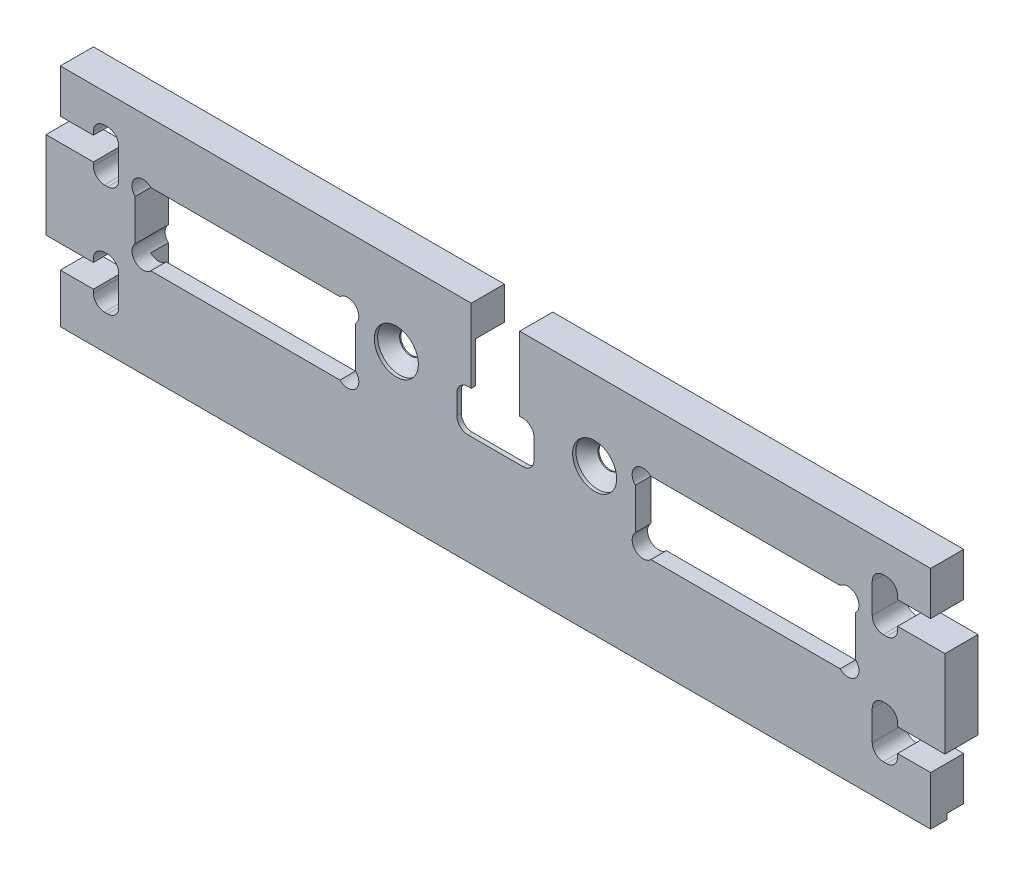
SolidWorks part; units mm, degrees
ref_plane "Front Plane" through (0, 0, 0) normal (0, 0, 1) x (1, 0, 0)
ref_plane "Top Plane" through (0, 0, 0) normal (0, 1, 0) x (1, 0, 0)
ref_plane "Right Plane" through (0, 0, 0) normal (1, 0, 0) x (0, 0, -1)
sketch "Sketch1" plane through (0, 0, 0) normal (0, 0, 1) x (1, 0, 0)
  line L0 (-39.5, 0) -> (39.5, 0) construction
  line L1 (-39.5, 10) -> (39.5, 10)
  line L2 (-39.5, 10) -> (-39.5, -10)
  line L3 (-39.5, -10) -> (39.5, -10)
  line L4 (39.5, 10) -> (39.5, -10)
  line L5 (-39.5, 10) -> (39.5, -10) construction
  line L6 (-39.5, -10) -> (39.5, 10) construction
  line L7 (0, 10) -> (0, -10) construction
  line L9 (-40.8, -3.95) -> (-39.5, -3.95)
  line L10 (-40.8, -3.95) -> (-40.8, 3.95)
  line L11 (-40.8, 3.95) -> (-39.5, 3.95)
  line L12 (-39.5, -3.95) -> (-39.5, 3.95)
  line L13 (-40.8, -3.95) -> (-39.5, 3.95) construction
  line L14 (-40.8, 3.95) -> (-39.5, -3.95) construction
  line L16 (40.8, 3.95) -> (39.5, 3.95)
  line L17 (40.8, -3.95) -> (40.8, 3.95)
  line L18 (40.8, -3.95) -> (39.5, -3.95)
  line L19 (-39.5, 5) -> (39.5, 5) construction
  line L20 (-35.35, 7.35) -> (-35.35, 2.65) construction
  line L21 (-36.5, 3.95) -> (-39.5, 3.95)
  line L22 (-36.5, 3.95) -> (-36.5, 6.05)
  line L23 (-36.5, 6.05) -> (-39.5, 6.05)
  line L24 (-39.5, 3.95) -> (-39.5, 6.05)
  line L25 (-36.5, 3.95) -> (-39.5, 6.05) construction
  line L26 (-36.5, 6.05) -> (-39.5, 3.95) construction
  line L27 (-34.2, 7.35) -> (-36.5, 7.35)
  line L28 (-34.2, 7.35) -> (-34.2, 2.65)
  line L29 (-34.2, 2.65) -> (-36.5, 2.65)
  line L30 (-36.5, 7.35) -> (-36.5, 2.65)
  line L31 (-34.2, 7.35) -> (-36.5, 2.65) construction
  line L32 (-34.2, 2.65) -> (-36.5, 7.35) construction
  line L33 (-34.2, -7.35) -> (-36.5, -7.35)
  line L34 (-34.2, -7.35) -> (-34.2, -2.65)
  line L35 (-34.2, -2.65) -> (-36.5, -2.65)
  line L36 (-36.5, -7.35) -> (-36.5, -2.65)
  line L37 (-36.5, -3.95) -> (-39.5, -3.95)
  line L38 (-36.5, -6.05) -> (-39.5, -6.05)
  line L39 (36.5, 3.95) -> (39.5, 3.95)
  line L40 (36.5, 6.05) -> (39.5, 6.05)
  line L41 (36.5, 7.35) -> (36.5, 2.65)
  line L42 (34.2, 7.35) -> (36.5, 7.35)
  line L43 (34.2, 7.35) -> (34.2, 2.65)
  line L44 (34.2, 2.65) -> (36.5, 2.65)
  line L45 (34.2, -2.65) -> (36.5, -2.65)
  line L46 (34.2, -7.35) -> (34.2, -2.65)
  line L47 (34.2, -7.35) -> (36.5, -7.35)
  line L48 (36.5, -7.35) -> (36.5, -2.65)
  line L49 (36.5, -6.05) -> (39.5, -6.05)
  line L50 (36.5, -3.95) -> (39.5, -3.95)
  point P0 (0, 0)
  point P10 (-40.15, 0)
  point P15 (-38, 5)
  point P35 (-35.35, 5)
  dimension "D1" = 79
  dimension "D2" = 20
  dimension "D4" = 1.3
  dimension "D7" = 5
  dimension "D8" = 2.1
  dimension "D9" = 3
  dimension "D10" = 2.3
  dimension "D11" = 4.7
extrude "Base shape" add sketch "Sketch1" along normal blind 3 contours L4 L1 L2 L3 | L9 L2 L11 L10 | L16 L4 L18 L17 region at (0, 0, 0) region at (-40.15, 0, 0) region at (40.15, 0, 0)
sketch "Sketch4" plane through (0, -10, 0) normal (0, -1, 0) x (1, 0, 0)
  line L0 (39.5, 3) -> (39.5, 0) construction
  line L1 (-39.5, 3) -> (39.5, 3)
  line L2 (-39.5, 3) -> (-39.5, 1.5)
  line L3 (-39.5, 1.5) -> (39.5, 1.5)
  line L4 (39.5, 3) -> (39.5, 1.5)
extrude "Floor lip" add sketch "Sketch4" along normal blind 0.5
sketch "Sketch6" plane through (0, 0, 0) normal (0, 0, -1) x (-1, 0, 0)
  line L0 (0, 0) -> (0, -10) construction
  line L1 (39.5, -10) -> (-39.5, -10) construction
  line L2 (-4, -10) -> (4, -10) construction
  line L3 (39.5, -10) -> (-39.5, -10) construction
  line L4 (-4, -9) -> (4, -9)
  line L5 (-4, -11) -> (4, -11)
  arc A0 (-4, -9) -> (-4, -11) centre (-4, -10) ccw
  arc A1 (4, -11) -> (4, -9) centre (4, -10) ccw
  point P9 (0, -10)
  dimension "D1" = 2
  dimension "D2" = 8
extrude "Nail cutout" cut sketch "Sketch6" against normal up to surface (1.5 mm away) up to face at (0, -10.25, 1.5)
sketch "Sketch3" plane through (-40.8, 0, 0) normal (-1, 0, 0) x (0, 0, 1)
  line L0 (0, 6.05) -> (3, 3.95) construction
  line L1 (0, 6.05) -> (3, 6.05)
  line L2 (0, 6.05) -> (0, 3.95)
  line L3 (0, 3.95) -> (3, 3.95)
  line L4 (3, 6.05) -> (3, 3.95)
  line L5 (0, -3.95) -> (3, -6.05) construction
  line L6 (0, -3.95) -> (3, -3.95)
  line L7 (0, -3.95) -> (0, -6.05)
  line L8 (0, -6.05) -> (3, -6.05)
  line L9 (3, -3.95) -> (3, -6.05)
  point P6 (1.5, 5)
  point P13 (1.5, -5)
ref_axis "Tap axis top" through (-53.7846, 5, 1.5) along (1, 0, 0)
ref_axis "Tap axis bottom" through (-54.2844, -5, 1.5) along (1, 0, 0)
fillet "Mill fillets" radius 1 16 edges at (36.5, -7.35, 1.5) (36.5, 2.65, 1.5) (34.2, 2.65, 1.5) (34.2, -7.35, 1.5) (36.5, -2.65, 1.5) (36.5, 7.35, 1.5) (34.2, -2.65, 1.5) (34.2, 7.35, 1.5) (-36.5, -2.65, 1.5) (-34.2, -2.65, 1.5) (-34.2, -7.35, 1.5) (-36.5, -7.35, 1.5) (-36.5, 2.65, 1.5) (-34.2, 2.65, 1.5) (-34.2, 7.35, 1.5) (-36.5, 7.35, 1.5)
sketch "Sketch8" [suppressed] plane through (0, 0, 3) normal (0, 0, 1) x (1, 0, 0)
  line L0 (-40.8, 0) -> (40.8, 0) construction
  line L1 (-40.8, -3.95) -> (-40.8, 3.95) construction
  line L2 (40.8, -3.95) -> (40.8, 3.95) construction
  line L4 (-24.5, 5.15) -> (24.5, 5.15)
  line L5 (-25.5, 4.15) -> (-25.5, -4.15)
  line L6 (-24.5, -5.15) -> (24.5, -5.15)
  line L7 (25.5, 4.15) -> (25.5, -4.15)
  line L8 (-25.5, 5.15) -> (25.5, -5.15) construction
  line L9 (-25.5, -5.15) -> (25.5, 5.15) construction
  arc A0 (24.5, -5.15) -> (25.5, -4.15) centre (24.5, -4.15) ccw
  arc A1 (24.5, 5.15) -> (25.5, 4.15) centre (24.5, 4.15) cw
  arc A2 (-25.5, -4.15) -> (-24.5, -5.15) centre (-24.5, -4.15) ccw
  arc A3 (-24.5, 5.15) -> (-25.5, 4.15) centre (-24.5, 4.15) ccw
  point P6 (0, 0)
  dimension "D3" = 1
  dimension "D1" = 51
  dimension "D2" = 10.3
extrude "Led strip pocket" [suppressed] cut sketch "Sketch8" against normal offset from surface (2.5 mm away) 0.5 up to face at (0, -0.6712, 0)
sketch "Sketch9" [suppressed] plane through (0, 0, 0.5) normal (0, 0, 1) x (1, 0, 0)
  line L0 (-19.5, 5.15) -> (-19.5, -5.15)
  line L1 (0, 5.15) -> (0, -5.15) construction
  line L2 (19.5, 5.15) -> (19.5, -5.15)
  line L3 (-25.5, -2.978) -> (25.5, -2.978) construction
  line L4 (25.5, -4.15) -> (25.5, 4.15)
  line L5 (24.5, 5.15) -> (-24.5, 5.15)
  line L6 (-25.5, 4.15) -> (-25.5, -4.15)
  line L7 (-24.5, -5.15) -> (24.5, -5.15)
  line L8 (25.5, -4.15) -> (25.5, 4.15)
  line L9 (24.5, 5.15) -> (-24.5, 5.15)
  line L10 (-25.5, 4.15) -> (-25.5, -4.15)
  line L11 (-24.5, -5.15) -> (24.5, -5.15)
  circle A0 centre (-12.7, -2.978) radius 1
  circle A1 centre (12.7, -2.978) radius 1
  arc A4 (24.5, -5.15) -> (25.5, -4.15) centre (24.5, -4.15) ccw
  arc A5 (25.5, 4.15) -> (24.5, 5.15) centre (24.5, 4.15) ccw
  arc A6 (-24.5, 5.15) -> (-25.5, 4.15) centre (-24.5, 4.15) ccw
  arc A7 (-25.5, -4.15) -> (-24.5, -5.15) centre (-24.5, -4.15) ccw
  arc A8 (24.5, -5.15) -> (25.5, -4.15) centre (24.5, -4.15) ccw
  arc A9 (25.5, 4.15) -> (24.5, 5.15) centre (24.5, 4.15) ccw
  arc A10 (-24.5, 5.15) -> (-25.5, 4.15) centre (-24.5, 4.15) ccw
  arc A11 (-25.5, -4.15) -> (-24.5, -5.15) centre (-24.5, -4.15) ccw
  arc M13 (24.5, -5.15) -> (25.5, -4.15) centre (24.5, -4.15) ccw
  line M14 (25.5, -4.15) -> (25.5, 4.15)
  arc M15 (25.5, 4.15) -> (24.5, 5.15) centre (24.5, 4.15) ccw
  line M16 (24.5, 5.15) -> (-24.5, 5.15)
  arc M17 (-24.5, 5.15) -> (-25.5, 4.15) centre (-24.5, 4.15) ccw
  line M18 (-25.5, 4.15) -> (-25.5, -4.15)
  arc M19 (-25.5, -4.15) -> (-24.5, -5.15) centre (-24.5, -4.15) ccw
  line M20 (-24.5, -5.15) -> (24.5, -5.15)
  dimension "D4" = 2
  dimension "D2" = 6
  dimension "D3" = 8.128
  dimension "D5" = 25.4
  dimension "D1" = 0
extrude "Led strip cuts" [suppressed] cut sketch "Sketch9" against normal up to next contours L0 M16 M17 M18 M19 M20 | L2 M16 M20 M13 M14 M15 | A0 | A1
fillet "Led strip cut fillets" [suppressed] radius 1
sketch "Sketch13" plane through (0, 0, 0) normal (0, 0, -1) x (-1, 0, 0)
  line L0 (0, 15.8648) -> (0, -21.9195) construction
  line L2 (-4.2, -6.3) -> (4.2, -6.3)
  line L3 (-5.2, -5.3) -> (-5.2, 6)
  line L4 (-4.2, 7) -> (4.2, 7)
  line L5 (5.2, -5.3) -> (5.2, 6)
  line L6 (-5.2, -6.3) -> (5.2, 7) construction
  line L7 (-5.2, 7) -> (5.2, -6.3) construction
  line L10 (39.5, 10) -> (-39.5, 10) construction
  arc A0 (-4.2, -6.3) -> (-5.2, -5.3) centre (-4.2, -5.3) cw
  arc A1 (4.2, -6.3) -> (5.2, -5.3) centre (4.2, -5.3) ccw
  arc A4 (5.2, 6) -> (4.2, 7) centre (4.2, 6) ccw
  arc A5 (-5.2, 6) -> (-4.2, 7) centre (-4.2, 6) cw
  point P1 (0, 0.35)
  dimension "D4" = 1
  dimension "D5" = 1
  dimension "D1" = 10.4
  dimension "D2" = 13.3
  dimension "D3" = 3
extrude "Bumper mount inner cut" cut sketch "Sketch13" against normal offset from surface (2.6 mm away) 0.4 up to face at (0, -0.0192, 3)
sketch "Sketch14" plane through (0, 0, 0) normal (0, 0, -1) x (-1, 0, 0)
  line L1 (0, 12.9528) -> (0, -14.0841) construction
  line L2 (4.2, 7) -> (-4.2, 7) construction
  line L3 (-4.2, -6.3) -> (4.2, -6.3) construction
  line L4 (-11.7, 7) -> (11.7, 7)
  line L5 (-12.7, 6) -> (-12.7, -5.3)
  line L6 (-11.7, -6.3) -> (11.7, -6.3)
  line L7 (12.7, 6) -> (12.7, -5.3)
  line L8 (-12.7, 7) -> (12.7, -6.3) construction
  line L9 (-12.7, -6.3) -> (12.7, 7) construction
  arc A1 (11.7, -6.3) -> (12.7, -5.3) centre (11.7, -5.3) ccw
  arc A2 (-12.7, -5.3) -> (-11.7, -6.3) centre (-11.7, -5.3) ccw
  arc A3 (11.7, 7) -> (12.7, 6) centre (11.7, 6) cw
  arc A4 (-12.7, 6) -> (-11.7, 7) centre (-11.7, 6) cw
  point P6 (0, 0.35)
  dimension "D2" = 1
  dimension "D3" = 1
  dimension "D1" = 25.4
extrude "Bumper mount outer cut" cut sketch "Sketch14" against normal blind 1.6
sketch "Sketch15" plane through (0, 0, 1.6) normal (0, 0, -1) x (-1, 0, 0)
  line L0 (-12.7, 2.8) -> (12.7, 2.8) construction
  line L3 (0, 16.4744) -> (0, -20.0474) construction
  line L7 (-12.7, 6) -> (-12.7, -5.3) construction
  line L8 (12.7, -5.3) -> (12.7, 6) construction
  line L11 (-4.2, 7) -> (-11.7, 7) construction
  circle A0 centre (-9, 2.8) radius 1
  circle A1 centre (9, 2.8) radius 1
  dimension "D1" = 18
  dimension "D2" = 2
  dimension "D3" = 4.2
extrude "Bumper mount screw holes" cut sketch "Sketch15" against normal up to next
sketch "Sketch16" plane through (0, 0, 2.6) normal (0, 0, -1) x (-1, 0, 0)
  line L0 (-5.2, 1.4) -> (5.2, 1.4) construction
  line L3 (0, 7) -> (0, -4.2) construction
  line L4 (-2.5, 3.3) -> (2.5, 3.3)
  line L5 (-3.5, 2.3) -> (-3.5, 0.5)
  line L6 (-2.5, -0.5) -> (2.5, -0.5)
  line L7 (3.5, 2.3) -> (3.5, 0.5)
  line L8 (-3.5, 3.3) -> (3.5, -0.5) construction
  line L9 (-3.5, -0.5) -> (3.5, 3.3) construction
  line L11 (-5.2, 6) -> (-5.2, -5.3) construction
  line L13 (4.2, 7) -> (-4.2, 7) construction
  arc A0 (2.5, -0.5) -> (3.5, 0.5) centre (2.5, 0.5) ccw
  arc A1 (-3.5, 0.5) -> (-2.5, -0.5) centre (-2.5, 0.5) ccw
  arc A2 (-2.5, 3.3) -> (-3.5, 2.3) centre (-2.5, 2.3) ccw
  arc A3 (2.5, 3.3) -> (3.5, 2.3) centre (2.5, 2.3) cw
  point P6 (0, 1.4)
  dimension "D3" = 1
  dimension "D1" = 7
  dimension "D2" = 3.8
  dimension "D4" = 11.2
extrude "Bumper body cut" cut sketch "Sketch16" against normal up to next
hole_wizard "Bumper screw countersunks" positions "Sketch17" profile "Sketch18" countersink size "M2" standard "ANSI Metric" end condition through all
sketch "Sketch17" plane through (0, 0, 3) normal (0, 0, 1) x (1, 0, 0)
  point P0 (9, 2.8)
  point P3 (-9, 2.8)
sketch "Sketch18" plane through (9, 2.8, 3) normal (1, 0, 0) x (0, -1, 0)
  line L0 (0, 0) -> (0, 3)
  line L1 (0, 3) -> (1, 3)
  line L2 (1, 3) -> (1, 1.3)
  line L3 (1, 1.3) -> (2, 0.3)
  line L4 (2, 0.3) -> (2, 0)
  line L6 (2, 0) -> (0, 0)
  line L7 (-1, 1.3) -> (-2, 0.3) construction
  line L11 (0, -6.35) -> (0, 107.95) construction
  dimension "Thru Hole Dia." = 2
  dimension "Thru Hole Depth" = 3
  dimension "C'Sink Dia." = 4
  dimension "C'Sink Angle" = 90
  dimension "Head Clearance" = 0.3
sketch "Sketch19" plane through (0, 0, 0) normal (0, 0, -1) x (-1, 0, 0)
  line L0 (0, 15.6498) -> (0, -12.9575) construction
  line L1 (39.5, 10) -> (-39.5, 10) construction
  line L2 (-2.2, 3.3) -> (2.2, 3.3)
  line L3 (-2.2, 3.3) -> (-2.2, 10)
  line L4 (-2.2, 10) -> (2.2, 10)
  line L5 (2.2, 3.3) -> (2.2, 10)
  line L6 (-2.2, 3.3) -> (2.2, 10) construction
  line L7 (-2.2, 10) -> (2.2, 3.3) construction
  line L8 (2.5, 3.3) -> (-2.5, 3.3) construction
  point P1 (0, 6.65)
  dimension "D1" = 4.4
extrude "Bumper insertion cut" cut sketch "Sketch19" against normal up to next
sketch "Sketch20" plane through (0, 0, 0) normal (0, 0, -1) x (-1, 0, 0)
  line L0 (-12.7, 6) -> (-12.7, -5.3) construction
  line L1 (-12.7, 4.55) -> (-32.7, 4.55)
  line L2 (-12.7, 4.55) -> (-12.7, -2)
  line L3 (-12.7, -2) -> (-32.7, -2)
  line L4 (-32.7, 4.55) -> (-32.7, -2)
  line L5 (-2.2, 10) -> (-39.5, 10) construction
  line L6 (-12.7, 4.55) -> (-19.25, -2) construction
  line L7 (-22.7, 4.55) -> (-22.7, -2) construction
  line L8 (-32.7, 1.275) -> (-12.7, 1.275) construction
  line L9 (0, 16.176) -> (0, -15.99) construction
  line L10 (12.7, 4.55) -> (12.7, -2)
  line L11 (12.7, -2) -> (32.7, -2)
  line L12 (32.7, 4.55) -> (32.7, -2)
  line L13 (12.7, 4.55) -> (32.7, 4.55)
  circle A0 centre (-13.4071, 3.8429) radius 1
  circle A1 centre (-31.9929, 3.8429) radius 1
  circle A2 centre (-13.4071, -1.2929) radius 1
  circle A3 centre (-31.9929, -1.2929) radius 1
  circle A4 centre (13.4071, 3.8429) radius 1
  circle A5 centre (13.4071, -1.2929) radius 1
  circle A6 centre (31.9929, -1.2929) radius 1
  circle A7 centre (31.9929, 3.8429) radius 1
  dimension "D5" = 2
  dimension "D1" = 20
  dimension "D2" = 5.45
  dimension "D3" = 6.55
  dimension "D4" = 45
extrude "Bumper switches cut" cut sketch "Sketch20" against normal up to next contours L1 L4 L3 L2 | A1 | A3 | A0 | A2 | L13 L12 L11 L10 | A4 | A5 | A6 | A7
sketch "Sketch21" plane through (0, 0, 0) normal (0, 0, -1) x (-1, 0, 0)
  line L0 (-14.1142, -2) -> (-31.2858, -2) construction
  line L1 (-32.7, -2) -> (-12.7, -2)
  line L2 (-32.7, -2) -> (-32.7, -6.3)
  line L3 (-32.7, -6.3) -> (-12.7, -6.3)
  line L4 (-12.7, -2) -> (-12.7, -6.3)
  line L5 (-12.7, -2) -> (-12.7, -5.3) construction
  line L6 (-11.7, -6.3) -> (-4.2, -6.3) construction
  line L7 (-32.7, 3.1358) -> (-32.7, -0.5858) construction
  line L8 (-12.7, -6.3) -> (-11.7, -6.3)
  line L9 (-32.7, -6.3) -> (-28.4, -2) construction
  line L10 (0, 14.2019) -> (0, -15.3745) construction
  line L11 (12.7, -6.3) -> (11.7, -6.3)
  line L12 (12.7, -2) -> (12.7, -6.3)
  line L13 (32.7, -2) -> (12.7, -2)
  line L14 (32.7, -2) -> (32.7, -6.3)
  line L15 (32.7, -6.3) -> (12.7, -6.3)
  arc A0 (-12.7, -5.3) -> (-11.7, -6.3) centre (-11.7, -5.3) ccw construction
  arc A1 (-12.7, -5.3) -> (-11.7, -6.3) centre (-11.7, -5.3) ccw
  circle A2 centre (-31.9929, -5.5929) radius 1
  arc A3 (-32.7, -0.5858) -> (-31.2858, -2) centre (-31.9929, -1.2929) ccw construction
  circle A4 centre (31.9929, -5.5929) radius 1
  arc A5 (12.7, -5.3) -> (11.7, -6.3) centre (11.7, -5.3) cw
  dimension "D1" = 45
extrude "Bumper switch mounts cut" cut sketch "Sketch21" against normal up to surface (1.6 mm away) contours A1 L4 L8 | L12 A5 L11 | L4 L1 L2 L3 | A2 | L12 L13 L14 L15 | A4 region at (12.4766, -6.0766, 0) region at (-12.4766, -6.0766, 0) up to face at (-8, 2.8, 1.6)
sketch "Outer coordinate system sketch" plane through (0, 0, 3) normal (0, 0, 1) x (1, 0, 0)
  line L0 (-35.35, 7.35) -> (-35.35, 2.65) construction
  line L1 (-35.2, 7.35) -> (-35.5, 7.35) construction
  line L2 (-40.8, 3.95) -> (-40.8, 10) construction
  line L3 (-40.8, 10) -> (-39.5, 10) construction
  line L4 (-35.2, 2.65) -> (-35.5, 2.65) construction
  line L5 (0, 15.526) -> (0, -17.3739) construction
  line L6 (-51.2617, 0) -> (56.0692, 0) construction
  circle A0 centre (-35.35, 6.35) radius 1
  point P16 (-35.35, 6.35)
  point P22 (35.35, 6.35)
  point P24 (-35.35, -6.35)
  point P25 (35.35, -6.35)
  dimension "D1" = 2
sketch "Inner coordinate system sketch" plane through (0, 0, 0) normal (0, 0, 1) x (1, 0, 0)
  line L0 (-40.8, -3.95) -> (-40.8, -10) construction
  line L1 (-40.8, -10) -> (-39.5, -10) construction
  line L3 (0, 19.9465) -> (0, -19.5427) construction
  line L4 (53.9633, 0) -> (-51.6097, 0) construction
sketch "Deep inner pocket mill sketch" plane through (0, 0, 2.6) normal (0, 0, -1) x (-1, 0, 0)
  line L0 (-4.2, 7) -> (4.2, 7)
  line L12 (4.2, 7) -> (2.2, 7)
  line L13 (2.2, 7) -> (2.2, 3.3)
  line L14 (2.2, 3.3) -> (2.5, 3.3)
  line L15 (3.5, 2.3) -> (3.5, 0.5)
  line L16 (2.5, -0.5) -> (-2.5, -0.5)
  line L17 (-3.5, 0.5) -> (-3.5, 2.3)
  line L18 (-2.5, 3.3) -> (-2.2, 3.3)
  line L19 (-2.2, 3.3) -> (-2.2, 7)
  line L20 (-2.2, 7) -> (-4.2, 7)
  line L21 (-5.2, 6) -> (-5.2, -5.3)
  line L22 (-4.2, -6.3) -> (4.2, -6.3)
  line L23 (5.2, -5.3) -> (5.2, 6)
  line L33 (-5.2, 6) -> (-5.2, -5.3)
  line L34 (-4.2, -6.3) -> (4.2, -6.3)
  line L35 (5.2, -5.3) -> (5.2, 6)
  arc A8 (3.5, 2.3) -> (2.5, 3.3) centre (2.5, 2.3) ccw
  arc A9 (2.5, -0.5) -> (3.5, 0.5) centre (2.5, 0.5) ccw
  arc A10 (-3.5, 0.5) -> (-2.5, -0.5) centre (-2.5, 0.5) ccw
  arc A11 (-2.5, 3.3) -> (-3.5, 2.3) centre (-2.5, 2.3) ccw
  arc A12 (-4.2, 7) -> (-5.2, 6) centre (-4.2, 6) ccw
  arc A13 (-5.2, -5.3) -> (-4.2, -6.3) centre (-4.2, -5.3) ccw
  arc A14 (4.2, -6.3) -> (5.2, -5.3) centre (4.2, -5.3) ccw
  arc A15 (5.2, 6) -> (4.2, 7) centre (4.2, 6) ccw
  arc A20 (-4.2, 7) -> (-5.2, 6) centre (-4.2, 6) ccw
  arc A21 (-5.2, -5.3) -> (-4.2, -6.3) centre (-4.2, -5.3) ccw
  arc A22 (4.2, -6.3) -> (5.2, -5.3) centre (4.2, -5.3) ccw
  arc A23 (5.2, 6) -> (4.2, 7) centre (4.2, 6) ccw
  dimension "D1" = 0
sketch "Shallow inner pocket mill sketch" plane through (0, 0, 1.6) normal (0, 0, -1) x (-1, 0, 0)
  line L2 (12.7, 4.55) -> (12.7, 6) construction
  line L7 (-12.7, 6) -> (-12.7, 4.55) construction
  line L16 (12.7, 4.55) -> (12.7, 6)
  line L21 (-12.7, 6) -> (-12.7, 4.55)
  line L42 (-32.7, -1) -> (-13.7, -1)
  line L43 (-12.7, 3.1358) -> (-12.7, -0.5858) construction
  line L47 (0, 16.1275) -> (0, -14.7685) construction
  line L53 (-31.2858, -6.3) -> (31.2858, -6.3)
  line L54 (-11.7, 7) -> (11.7, 7)
  line L55 (-12.7, 4.55) -> (-13.7, 4.55)
  line L56 (-13.7, 4.55) -> (-13.7, -1)
  line L58 (-22.7, -2) -> (-22.7, -1) construction
  line L59 (-31.2858, -2) -> (-14.1142, -2) construction
  line L60 (-12.7, 1.275) -> (-13.7, 1.275) construction
  line L61 (-32.7, -1) -> (-32.7, -4.8858)
  line L62 (12.7, 4.55) -> (13.7, 4.55)
  line L63 (13.7, 4.55) -> (13.7, -1)
  line L64 (32.7, -1) -> (13.7, -1)
  line L65 (32.7, -1) -> (32.7, -4.8858)
  arc A2 (12.7, 6) -> (11.7, 7) centre (11.7, 6) ccw construction
  arc A5 (31.2858, -6.3) -> (32.7, -4.8858) centre (31.9929, -5.5929) ccw construction
  arc A10 (-32.7, -4.8858) -> (-31.2858, -6.3) centre (-31.9929, -5.5929) ccw construction
  arc A13 (-11.7, 7) -> (-12.7, 6) centre (-11.7, 6) ccw construction
  arc A16 (12.7, 6) -> (11.7, 7) centre (11.7, 6) ccw
  arc A19 (31.2858, -6.3) -> (32.7, -4.8858) centre (31.9929, -5.5929) ccw
  arc A24 (-32.7, -4.8858) -> (-31.2858, -6.3) centre (-31.9929, -5.5929) ccw
  arc A27 (-11.7, 7) -> (-12.7, 6) centre (-11.7, 6) ccw
  dimension "D1" = 1
